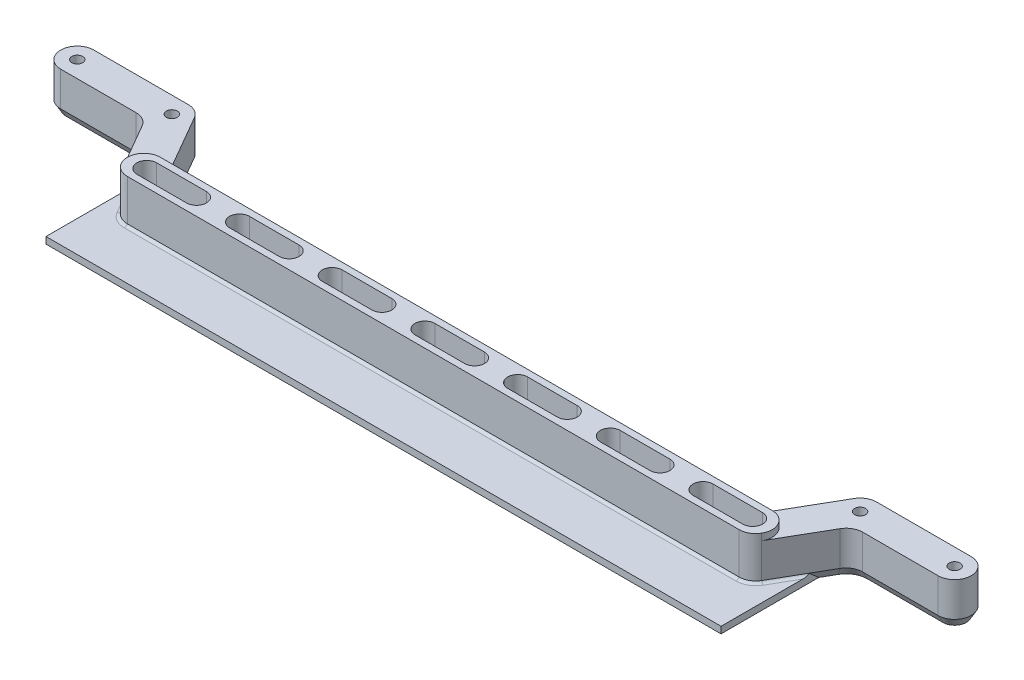
SolidWorks part; units mm, degrees
ref_plane "前视基准面" through (0, 0, 0) normal (0, 0, 1) x (1, 0, 0)
ref_plane "上视基准面" through (0, 0, 0) normal (0, 1, 0) x (1, 0, 0)
ref_plane "右视基准面" through (0, 0, 0) normal (1, 0, 0) x (0, 0, -1)
sketch "草图1" plane through (0, 0, 0) normal (0, 1, 0) x (1, 0, 0)
  line L0 (-14.275, 0) -> (14.275, 0) construction
  line L1 (-14.275, 5) -> (14.275, 5)
  line L2 (-14.275, -5) -> (14.275, -5)
  line L3 (14.275, 0) -> (25.822, -20) construction
  line L4 (25.822, -20) -> (210.628, -20) construction
  line L5 (14.275, 0) -> (25.822, -20) construction
  line L6 (18.6051, 2.5) -> (30.1521, -17.5)
  line L7 (9.9449, -2.5) -> (21.4919, -22.5)
  line L8 (25.822, -20) -> (210.628, -20) construction
  line L9 (25.822, -15) -> (210.628, -15)
  line L10 (25.822, -25) -> (210.628, -25)
  line L11 (210.628, -20) -> (222.175, 0) construction
  line L12 (206.2979, -17.5) -> (217.8449, 2.5)
  line L13 (214.9581, -22.5) -> (226.5051, -2.5)
  line L14 (222.175, 0) -> (250.725, 0) construction
  line L15 (222.175, 5) -> (250.725, 5)
  line L16 (222.175, -5) -> (250.725, -5)
  circle A0 centre (-14.275, 0) radius 1.65
  arc A1 (-14.275, 5) -> (-14.275, -5) centre (-14.275, 0) ccw
  arc A2 (14.275, -5) -> (14.275, 5) centre (14.275, 0) ccw
  arc A3 (18.6051, 2.5) -> (9.9449, -2.5) centre (14.275, 0) ccw
  arc A4 (21.4919, -22.5) -> (30.1521, -17.5) centre (25.822, -20) ccw
  arc A5 (25.822, -15) -> (25.822, -25) centre (25.822, -20) ccw
  arc A6 (210.628, -25) -> (210.628, -15) centre (210.628, -20) ccw
  circle A7 centre (14.275, 0) radius 1.65
  arc A8 (206.2979, -17.5) -> (214.9581, -22.5) centre (210.628, -20) ccw
  arc A9 (226.5051, -2.5) -> (217.8449, 2.5) centre (222.175, 0) ccw
  arc A10 (222.175, 5) -> (222.175, -5) centre (222.175, 0) ccw
  arc A11 (250.725, -5) -> (250.725, 5) centre (250.725, 0) ccw
  circle A12 centre (250.725, 0) radius 1.65
  circle A13 centre (222.175, 0) radius 1.65
  point P2 (0, 0)
  point P12 (20.0485, -10)
  point P18 (118.225, -20)
  point P27 (216.4015, -10)
  point P34 (236.45, 0)
  dimension "D1" = 3.3
  dimension "D2" = 5
  dimension "D7" = 3.3
  dimension "D11" = 3.3
  dimension "D12" = 3.3
  dimension "D3" = 28.55
  dimension "D4" = 20
  dimension "D5" = 120
  dimension "D6" = 120
  dimension "D8" = 20
  dimension "D9" = 28.55
  dimension "D10" = 207.9
extrude "凸台-拉伸1" add sketch "草图1" along normal blind 15 contours A3 L1 A1 L2 L7 A0 | A2 A3 L7 L2 | A5 L9 L6 A2 L2 L7 | L9 A5 A4 L6 | L10 A6 L9 L6 A4 | A10 L12 L9 A6 L13 L16 | L12 A8 A6 L9 | A9 A10 L16 L13 A13 | L16 A11 L15 A9 L13 A12 region at (-3.682, 0, -0.0218) region at (16.7043, 0, -4.2077) region at (20.0485, 0, 10) region at (118.225, 0, 20.0068) region at (25.8655, 0, 19.9247) region at (216.4015, 0, 10) region at (210.5845, 0, 19.9247) region at (219.7457, 0, -4.2077) region at (240.132, 0, -0.0218)
fillet "圆角1" radius 5 4 edges at (11.3882, 7.5, 5) (225.0618, 7.5, 5) (207.7412, 7.5, 15) (28.7088, 7.5, 15)
chamfer "倒角1" distance 1.5 angle 60 20 edges at (213.5147, 0, 5) (219.675, 0, -4.3301) (236.45, 0, -5) (255.725, 0, 0) (239.3368, 0, 5) (225.4485, 0, 5.6699) (219.2882, 0, 15) (213.128, 0, 24.3301) (118.225, 0, 25) (23.322, 0, 24.3301) (22.9353, 0, 5) (17.1618, 0, 15) (16.775, 0, -4.3301) (11.0015, 0, 5.6699) (0, 0, -5) (-2.8868, 0, 5) (-19.275, 0, 0) (207.3545, 0, 14.3301) (118.225, 0, 15) (29.0955, 0, 14.3301) first distance on face at (118.225, 0, 8)
sketch "草图3" plane through (0, 0, 0) normal (0, 1, 0) x (1, 0, 0)
  circle A0 centre (-14.275, 0) radius 2.5
  circle A1 centre (14.275, 0) radius 2.5
  circle A2 centre (14.275, 0) radius 1.65 construction
  circle A3 centre (-14.275, 0) radius 1.65 construction
  circle A4 centre (250.725, 0) radius 2.5
  circle A5 centre (222.175, 0) radius 2.5
  circle A6 centre (222.175, 0) radius 1.65 construction
  circle A7 centre (250.725, 0) radius 1.65 construction
  dimension "D1" = 5
  dimension "D2" = 5
  dimension "D3" = 5
  dimension "D4" = 5
extrude "切除-拉伸1" cut sketch "草图3" along normal blind 3
sketch "草图4" plane through (0, 15, 0) normal (0, 1, 0) x (1, 0, 0)
  line L0 (25.822, -25) -> (210.628, -25) construction
  line L1 (-49.5799, -15) -> (304.1802, -15)
  line L2 (-49.5799, -15) -> (-49.5799, 56.9164)
  line L3 (-49.5799, 56.9164) -> (304.1802, 56.9164)
  line L4 (304.1802, -15) -> (304.1802, 56.9164)
  dimension "D1" = 10
extrude "切除-拉伸2" cut sketch "草图4" against normal blind 2
fillet "圆角2" radius 5 2 edges at (17.1618, 14, 15) (219.2882, 14, 15)
sketch "草图5" plane through (0, 15, 0) normal (0, 1, 0) x (1, 0, 0)
  line L0 (110.725, -20) -> (125.725, -20) construction
  line L1 (110.725, -17) -> (125.725, -17)
  line L2 (110.725, -23) -> (125.725, -23)
  line L3 (118.225, -20) -> (118.225, -15) construction
  line L4 (25.822, -15) -> (210.628, -15) construction
  arc A0 (110.725, -17) -> (110.725, -23) centre (110.725, -20) ccw
  arc A1 (125.725, -23) -> (125.725, -17) centre (125.725, -20) ccw
  point P2 (118.225, -20)
  dimension "D2" = 3
  dimension "D1" = 5
  dimension "D3" = 15
extrude "切除-拉伸3" cut sketch "草图5" against normal blind 12
pattern_linear "阵列(线性)1" count 4 spacing 28 along (1, 0, 0) count 4 spacing 28 along (-1, 0, 0) of "切除-拉伸3"
sketch "草图6" plane through (0, 0, 0) normal (0, -1, 0) x (1, 0, 0)
  line L0 (210.628, 23.5) -> (25.822, 23.5) construction
  line L1 (25.5333, 23.5) -> (210.3393, 23.5)
  line L2 (16.275, 23) -> (16.275, 40)
  line L3 (16.275, 40) -> (220.175, 40)
  line L4 (220.175, 23.5) -> (220.175, 40)
  line L5 (25.822, 25) -> (210.628, 25) construction
  line L6 (220.175, 23.5) -> (220.175, 6.4641)
  line L7 (220.175, 6.4641) -> (210.3393, 23.5)
  line L8 (222.3193, 6.75) -> (213.6591, 21.75) construction
  line L9 (16.275, 23) -> (16.275, 7.4641)
  line L10 (16.275, 7.4641) -> (25.5333, 23.5)
  line L11 (22.7909, 21.75) -> (14.1307, 6.75) construction
  circle A0 centre (14.275, 0) radius 1.65 construction
  circle A1 centre (222.175, 0) radius 1.65 construction
  dimension "D1" = 15
  dimension "D2" = 2
  dimension "D3" = 2
  dimension "D4" = 2
  dimension "D5" = 1.5
extrude "凸台-拉伸2" add sketch "草图6" against normal blind 2
fillet "圆角3" radius 1 5 edges at (217.417, 2, 17.5504) (212.9553, 2, 24.0311) (118.225, 2, 24.6547) (23.4947, 2, 24.0311) (19.033, 2, 17.5504)
